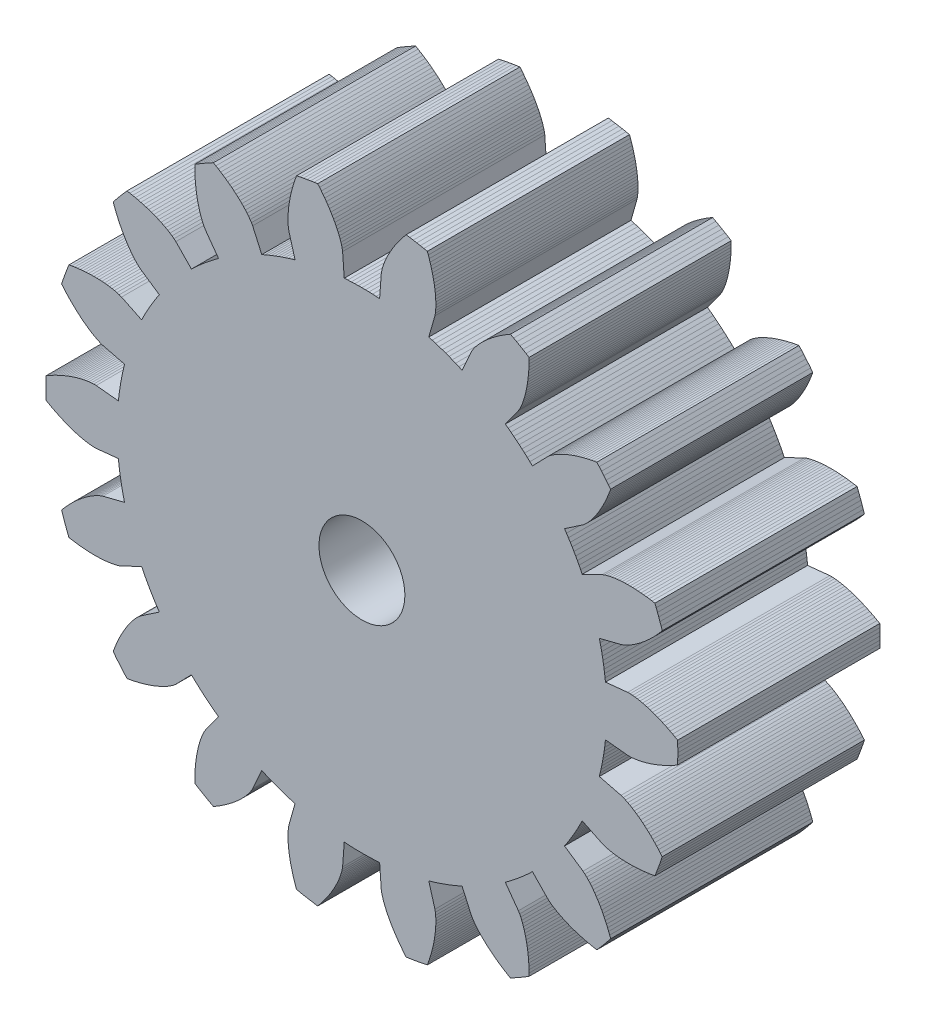
SolidWorks part; units mm, degrees
ref_plane "Front Plane" through (0, 0, 0) normal (0, 0, 1) x (1, 0, 0)
ref_plane "Top Plane" through (0, 0, 0) normal (0, 1, 0) x (1, 0, 0)
ref_plane "Right Plane" through (0, 0, 0) normal (1, 0, 0) x (0, 0, -1)
sketch "Gear Profile m1. 25 z18" plane through (0, 0, 0) normal (0, 0, 1) x (1, 0, 0)
  line L0 (9.637, -0.9881) -> (10.5164, -1.0782)
  line L1 (10.5164, -1.0782) -> (10.6132, -1.0794)
  line L2 (10.6132, -1.0794) -> (10.7108, -1.0732)
  line L3 (10.7108, -1.0732) -> (10.8087, -1.0622)
  line L4 (10.8087, -1.0622) -> (10.9071, -1.0471)
  line L5 (10.9071, -1.0471) -> (11.0057, -1.0284)
  line L6 (11.0057, -1.0284) -> (11.1046, -1.0065)
  line L7 (11.1046, -1.0065) -> (11.2036, -0.9815)
  line L8 (11.2036, -0.9815) -> (11.3028, -0.9536)
  line L9 (11.3028, -0.9536) -> (11.4021, -0.923)
  line L10 (11.4021, -0.923) -> (11.5014, -0.8897)
  line L11 (11.5014, -0.8897) -> (11.6008, -0.8539)
  line L12 (11.6008, -0.8539) -> (11.7002, -0.8156)
  line L13 (11.7002, -0.8156) -> (11.7996, -0.7749)
  line L14 (11.7996, -0.7749) -> (11.899, -0.7318)
  line L15 (11.899, -0.7318) -> (11.9983, -0.6864)
  line L16 (11.9983, -0.6864) -> (12.0975, -0.6387)
  line L17 (12.0975, -0.6387) -> (12.1965, -0.5888)
  line L18 (12.1965, -0.5888) -> (12.2954, -0.5367)
  line L19 (12.2954, -0.5367) -> (12.3942, -0.4824)
  line L20 (12.3942, -0.4824) -> (12.4927, -0.426)
  line L21 (12.4927, -0.426) -> (12.4968, -0.284)
  line L22 (12.4968, -0.284) -> (12.4992, -0.142)
  line L23 (12.4992, -0.142) -> (12.5, 0)
  line L24 (12.5, 0) -> (12.4992, 0.142)
  line L25 (12.4992, 0.142) -> (12.4968, 0.284)
  line L26 (12.4968, 0.284) -> (12.4927, 0.426)
  line L27 (12.4927, 0.426) -> (12.3942, 0.4824)
  line L28 (12.3942, 0.4824) -> (12.2954, 0.5367)
  line L29 (12.2954, 0.5367) -> (12.1965, 0.5888)
  line L30 (12.1965, 0.5888) -> (12.0975, 0.6387)
  line L31 (12.0975, 0.6387) -> (11.9983, 0.6864)
  line L32 (11.9983, 0.6864) -> (11.899, 0.7318)
  line L33 (11.899, 0.7318) -> (11.7996, 0.7749)
  line L34 (11.7996, 0.7749) -> (11.7002, 0.8156)
  line L35 (11.7002, 0.8156) -> (11.6008, 0.8539)
  line L36 (11.6008, 0.8539) -> (11.5014, 0.8897)
  line L37 (11.5014, 0.8897) -> (11.4021, 0.923)
  line L38 (11.4021, 0.923) -> (11.3028, 0.9536)
  line L39 (11.3028, 0.9536) -> (11.2036, 0.9815)
  line L40 (11.2036, 0.9815) -> (11.1046, 1.0065)
  line L41 (11.1046, 1.0065) -> (11.0057, 1.0284)
  line L42 (11.0057, 1.0284) -> (10.9071, 1.0471)
  line L43 (10.9071, 1.0471) -> (10.8087, 1.0622)
  line L44 (10.8087, 1.0622) -> (10.7108, 1.0732)
  line L45 (10.7108, 1.0732) -> (10.6132, 1.0794)
  line L46 (10.6132, 1.0794) -> (10.5164, 1.0782)
  line L47 (10.5164, 1.0782) -> (9.637, 0.9881)
  line L48 (9.637, 0.9881) -> (9.6217, 1.1274)
  line L49 (9.6217, 1.1274) -> (9.6043, 1.2665)
  line L50 (9.6043, 1.2665) -> (9.585, 1.4054)
  line L51 (9.585, 1.4054) -> (9.5637, 1.544)
  line L52 (9.5637, 1.544) -> (9.5403, 1.6822)
  line L53 (9.5403, 1.6822) -> (9.515, 1.8201)
  line L54 (9.515, 1.8201) -> (9.4876, 1.9576)
  line L55 (9.4876, 1.9576) -> (9.4583, 2.0947)
  line L56 (9.4583, 2.0947) -> (9.427, 2.2314)
  line L57 (9.427, 2.2314) -> (9.3937, 2.3676)
  line L58 (9.3937, 2.3676) -> (10.251, 2.5836)
  line L59 (10.251, 2.5836) -> (10.3423, 2.6156)
  line L60 (10.3423, 2.6156) -> (10.4319, 2.6548)
  line L61 (10.4319, 2.6548) -> (10.5202, 2.6987)
  line L62 (10.5202, 2.6987) -> (10.6074, 2.7465)
  line L63 (10.6074, 2.7465) -> (10.6937, 2.7978)
  line L64 (10.6937, 2.7978) -> (10.7791, 2.8522)
  line L65 (10.7791, 2.8522) -> (10.8636, 2.9096)
  line L66 (10.8636, 2.9096) -> (10.9473, 2.9697)
  line L67 (10.9473, 2.9697) -> (11.0301, 3.0324)
  line L68 (11.0301, 3.0324) -> (11.1121, 3.0977)
  line L69 (11.1121, 3.0977) -> (11.1932, 3.1653)
  line L70 (11.1932, 3.1653) -> (11.2736, 3.2353)
  line L71 (11.2736, 3.2353) -> (11.353, 3.3075)
  line L72 (11.353, 3.3075) -> (11.4317, 3.382)
  line L73 (11.4317, 3.382) -> (11.5095, 3.4586)
  line L74 (11.5095, 3.4586) -> (11.5864, 3.5373)
  line L75 (11.5864, 3.5373) -> (11.6624, 3.6181)
  line L76 (11.6624, 3.6181) -> (11.7375, 3.7009)
  line L77 (11.7375, 3.7009) -> (11.8117, 3.7857)
  line L78 (11.8117, 3.7857) -> (11.885, 3.8725)
  line L79 (11.885, 3.8725) -> (11.8403, 4.0073)
  line L80 (11.8403, 4.0073) -> (11.794, 4.1415)
  line L81 (11.794, 4.1415) -> (11.7462, 4.2753)
  line L82 (11.7462, 4.2753) -> (11.6968, 4.4084)
  line L83 (11.6968, 4.4084) -> (11.646, 4.541)
  line L84 (11.646, 4.541) -> (11.5936, 4.673)
  line L85 (11.5936, 4.673) -> (11.4817, 4.6924)
  line L86 (11.4817, 4.6924) -> (11.3704, 4.7096)
  line L87 (11.3704, 4.7096) -> (11.2596, 4.7248)
  line L88 (11.2596, 4.7248) -> (11.1494, 4.7378)
  line L89 (11.1494, 4.7378) -> (11.0399, 4.7487)
  line L90 (11.0399, 4.7487) -> (10.9311, 4.7574)
  line L91 (10.9311, 4.7574) -> (10.823, 4.7639)
  line L92 (10.823, 4.7639) -> (10.7157, 4.7681)
  line L93 (10.7157, 4.7681) -> (10.6091, 4.7701)
  line L94 (10.6091, 4.7701) -> (10.5035, 4.7698)
  line L95 (10.5035, 4.7698) -> (10.3987, 4.767)
  line L96 (10.3987, 4.767) -> (10.295, 4.7619)
  line L97 (10.295, 4.7619) -> (10.1923, 4.7541)
  line L98 (10.1923, 4.7541) -> (10.0906, 4.7437)
  line L99 (10.0906, 4.7437) -> (9.9903, 4.7306)
  line L100 (9.9903, 4.7306) -> (9.8912, 4.7144)
  line L101 (9.8912, 4.7144) -> (9.7936, 4.6949)
  line L102 (9.7936, 4.6949) -> (9.6978, 4.6718)
  line L103 (9.6978, 4.6718) -> (9.604, 4.6442)
  line L104 (9.604, 4.6442) -> (9.5134, 4.61)
  line L105 (9.5134, 4.61) -> (8.7179, 4.2245)
  line L106 (8.7179, 4.2245) -> (8.6558, 4.3502)
  line L107 (8.6558, 4.3502) -> (8.592, 4.475)
  line L108 (8.592, 4.475) -> (8.5263, 4.5989)
  line L109 (8.5263, 4.5989) -> (8.4588, 4.7218)
  line L110 (8.4588, 4.7218) -> (8.3896, 4.8438)
  line L111 (8.3896, 4.8438) -> (8.3186, 4.9647)
  line L112 (8.3186, 4.9647) -> (8.2459, 5.0845)
  line L113 (8.2459, 5.0845) -> (8.1715, 5.2033)
  line L114 (8.1715, 5.2033) -> (8.0953, 5.321)
  line L115 (8.0953, 5.321) -> (8.0175, 5.4376)
  line L116 (8.0175, 5.4376) -> (8.7491, 5.9339)
  line L117 (8.7491, 5.9339) -> (8.824, 5.9952)
  line L118 (8.824, 5.9952) -> (8.8948, 6.0626)
  line L119 (8.8948, 6.0626) -> (8.9627, 6.1341)
  line L120 (8.9627, 6.1341) -> (9.0284, 6.2088)
  line L121 (9.0284, 6.2088) -> (9.0919, 6.2865)
  line L122 (9.0919, 6.2865) -> (9.1535, 6.3669)
  line L123 (9.1535, 6.3669) -> (9.2133, 6.4497)
  line L124 (9.2133, 6.4497) -> (9.2714, 6.5348)
  line L125 (9.2714, 6.5348) -> (9.3278, 6.6221)
  line L126 (9.3278, 6.6221) -> (9.3825, 6.7114)
  line L127 (9.3825, 6.7114) -> (9.4356, 6.8027)
  line L128 (9.4356, 6.8027) -> (9.4872, 6.896)
  line L129 (9.4872, 6.896) -> (9.5371, 6.991)
  line L130 (9.5371, 6.991) -> (9.5856, 7.0879)
  line L131 (9.5856, 7.0879) -> (9.6324, 7.1865)
  line L132 (9.6324, 7.1865) -> (9.6778, 7.2868)
  line L133 (9.6778, 7.2868) -> (9.7216, 7.3887)
  line L134 (9.7216, 7.3887) -> (9.7638, 7.4922)
  line L135 (9.7638, 7.4922) -> (9.8046, 7.5973)
  line L136 (9.8046, 7.5973) -> (9.8438, 7.7039)
  line L137 (9.8438, 7.7039) -> (9.7556, 7.8152)
  line L138 (9.7556, 7.8152) -> (9.6662, 7.9255)
  line L139 (9.6662, 7.9255) -> (9.5756, 8.0348)
  line L140 (9.5756, 8.0348) -> (9.4837, 8.1431)
  line L141 (9.4837, 8.1431) -> (9.3905, 8.2503)
  line L142 (9.3905, 8.2503) -> (9.2962, 8.3565)
  line L143 (9.2962, 8.3565) -> (9.1844, 8.3364)
  line L144 (9.1844, 8.3364) -> (9.0739, 8.3145)
  line L145 (9.0739, 8.3145) -> (8.9646, 8.2908)
  line L146 (8.9646, 8.2908) -> (8.8566, 8.2654)
  line L147 (8.8566, 8.2654) -> (8.75, 8.2382)
  line L148 (8.75, 8.2382) -> (8.6447, 8.2091)
  line L149 (8.6447, 8.2091) -> (8.5409, 8.1783)
  line L150 (8.5409, 8.1783) -> (8.4386, 8.1456)
  line L151 (8.4386, 8.1456) -> (8.3379, 8.111)
  line L152 (8.3379, 8.111) -> (8.2387, 8.0745)
  line L153 (8.2387, 8.0745) -> (8.1412, 8.0361)
  line L154 (8.1412, 8.0361) -> (8.0455, 7.9958)
  line L155 (8.0455, 7.9958) -> (7.9516, 7.9534)
  line L156 (7.9516, 7.9534) -> (7.8597, 7.9089)
  line L157 (7.8597, 7.9089) -> (7.7698, 7.8621)
  line L158 (7.7698, 7.8621) -> (7.6823, 7.813)
  line L159 (7.6823, 7.813) -> (7.5972, 7.7614)
  line L160 (7.5972, 7.7614) -> (7.5151, 7.7069)
  line L161 (7.5151, 7.7069) -> (7.4364, 7.6489)
  line L162 (7.4364, 7.6489) -> (7.363, 7.5858)
  line L163 (7.363, 7.5858) -> (6.7472, 6.9514)
  line L164 (6.7472, 6.9514) -> (6.6459, 7.0483)
  line L165 (6.6459, 7.0483) -> (6.5432, 7.1438)
  line L166 (6.5432, 7.1438) -> (6.4392, 7.2377)
  line L167 (6.4392, 7.2377) -> (6.3337, 7.3302)
  line L168 (6.3337, 7.3302) -> (6.227, 7.4211)
  line L169 (6.227, 7.4211) -> (6.119, 7.5104)
  line L170 (6.119, 7.5104) -> (6.0096, 7.5982)
  line L171 (6.0096, 7.5982) -> (5.899, 7.6843)
  line L172 (5.899, 7.6843) -> (5.7872, 7.7689)
  line L173 (5.7872, 7.7689) -> (5.6742, 7.8518)
  line L174 (5.6742, 7.8518) -> (6.192, 8.5684)
  line L175 (6.192, 8.5684) -> (6.2414, 8.6516)
  line L176 (6.2414, 8.6516) -> (6.2848, 8.7392)
  line L177 (6.2848, 8.7392) -> (6.3242, 8.8296)
  line L178 (6.3242, 8.8296) -> (6.3603, 8.9223)
  line L179 (6.3603, 8.9223) -> (6.3935, 9.017)
  line L180 (6.3935, 9.017) -> (6.4239, 9.1136)
  line L181 (6.4239, 9.1136) -> (6.4518, 9.2119)
  line L182 (6.4518, 9.2119) -> (6.4772, 9.3117)
  line L183 (6.4772, 9.3117) -> (6.5003, 9.413)
  line L184 (6.5003, 9.413) -> (6.5212, 9.5157)
  line L185 (6.5212, 9.5157) -> (6.5399, 9.6196)
  line L186 (6.5399, 9.6196) -> (6.5565, 9.7249)
  line L187 (6.5565, 9.7249) -> (6.5709, 9.8313)
  line L188 (6.5709, 9.8313) -> (6.5833, 9.9389)
  line L189 (6.5833, 9.9389) -> (6.5936, 10.0476)
  line L190 (6.5936, 10.0476) -> (6.6019, 10.1573)
  line L191 (6.6019, 10.1573) -> (6.6082, 10.2681)
  line L192 (6.6082, 10.2681) -> (6.6125, 10.3798)
  line L193 (6.6125, 10.3798) -> (6.6149, 10.4925)
  line L194 (6.6149, 10.4925) -> (6.6153, 10.6061)
  line L195 (6.6153, 10.6061) -> (6.4943, 10.6805)
  line L196 (6.4943, 10.6805) -> (6.3726, 10.7536)
  line L197 (6.3726, 10.7536) -> (6.25, 10.8253)
  line L198 (6.25, 10.8253) -> (6.1266, 10.8956)
  line L199 (6.1266, 10.8956) -> (6.0024, 10.9645)
  line L200 (6.0024, 10.9645) -> (5.8775, 11.032)
  line L201 (5.8775, 11.032) -> (5.7793, 10.9749)
  line L202 (5.7793, 10.9749) -> (5.6829, 10.9165)
  line L203 (5.6829, 10.9165) -> (5.5883, 10.8569)
  line L204 (5.5883, 10.8569) -> (5.4956, 10.7961)
  line L205 (5.4956, 10.7961) -> (5.4047, 10.734)
  line L206 (5.4047, 10.734) -> (5.3157, 10.6707)
  line L207 (5.3157, 10.6707) -> (5.2287, 10.6062)
  line L208 (5.2287, 10.6062) -> (5.1438, 10.5405)
  line L209 (5.1438, 10.5405) -> (5.0609, 10.4735)
  line L210 (5.0609, 10.4735) -> (4.9802, 10.4054)
  line L211 (4.9802, 10.4054) -> (4.9017, 10.336)
  line L212 (4.9017, 10.336) -> (4.8255, 10.2653)
  line L213 (4.8255, 10.2653) -> (4.7518, 10.1933)
  line L214 (4.7518, 10.1933) -> (4.6807, 10.1201)
  line L215 (4.6807, 10.1201) -> (4.6122, 10.0454)
  line L216 (4.6122, 10.0454) -> (4.5468, 9.9694)
  line L217 (4.5468, 9.9694) -> (4.4845, 9.8917)
  line L218 (4.4845, 9.8917) -> (4.4259, 9.8124)
  line L219 (4.4259, 9.8124) -> (4.3718, 9.731)
  line L220 (4.3718, 9.731) -> (4.3244, 9.6466)
  line L221 (4.3244, 9.6466) -> (3.9628, 8.8399)
  line L222 (3.9628, 8.8399) -> (3.8345, 8.8963)
  line L223 (3.8345, 8.8963) -> (3.7053, 8.9509)
  line L224 (3.7053, 8.9509) -> (3.5754, 9.0036)
  line L225 (3.5754, 9.0036) -> (3.4447, 9.0544)
  line L226 (3.4447, 9.0544) -> (3.3133, 9.1033)
  line L227 (3.3133, 9.1033) -> (3.1812, 9.1503)
  line L228 (3.1812, 9.1503) -> (3.0485, 9.1953)
  line L229 (3.0485, 9.1953) -> (2.9151, 9.2385)
  line L230 (2.9151, 9.2385) -> (2.7811, 9.2797)
  line L231 (2.7811, 9.2797) -> (2.6465, 9.319)
  line L232 (2.6465, 9.319) -> (2.888, 10.1694)
  line L233 (2.888, 10.1694) -> (2.9059, 10.2645)
  line L234 (2.9059, 10.2645) -> (2.9168, 10.3617)
  line L235 (2.9168, 10.3617) -> (2.923, 10.4601)
  line L236 (2.923, 10.4601) -> (2.9252, 10.5596)
  line L237 (2.9252, 10.5596) -> (2.9239, 10.6599)
  line L238 (2.9239, 10.6599) -> (2.9195, 10.7611)
  line L239 (2.9195, 10.7611) -> (2.912, 10.863)
  line L240 (2.912, 10.863) -> (2.9018, 10.9655)
  line L241 (2.9018, 10.9655) -> (2.8889, 11.0686)
  line L242 (2.8889, 11.0686) -> (2.8734, 11.1722)
  line L243 (2.8734, 11.1722) -> (2.8554, 11.2763)
  line L244 (2.8554, 11.2763) -> (2.8349, 11.3808)
  line L245 (2.8349, 11.3808) -> (2.8121, 11.4858)
  line L246 (2.8121, 11.4858) -> (2.7869, 11.5911)
  line L247 (2.7869, 11.5911) -> (2.7595, 11.6968)
  line L248 (2.7595, 11.6968) -> (2.7297, 11.8028)
  line L249 (2.7297, 11.8028) -> (2.6978, 11.909)
  line L250 (2.6978, 11.909) -> (2.6636, 12.0155)
  line L251 (2.6636, 12.0155) -> (2.6273, 12.1221)
  line L252 (2.6273, 12.1221) -> (2.5888, 12.229)
  line L253 (2.5888, 12.229) -> (2.4497, 12.2576)
  line L254 (2.4497, 12.2576) -> (2.3103, 12.2846)
  line L255 (2.3103, 12.2846) -> (2.1706, 12.3101)
  line L256 (2.1706, 12.3101) -> (2.0306, 12.334)
  line L257 (2.0306, 12.334) -> (1.8904, 12.3562)
  line L258 (1.8904, 12.3562) -> (1.7499, 12.3769)
  line L259 (1.7499, 12.3769) -> (1.6771, 12.2897)
  line L260 (1.6771, 12.2897) -> (1.6065, 12.2018)
  line L261 (1.6065, 12.2018) -> (1.538, 12.1135)
  line L262 (1.538, 12.1135) -> (1.4717, 12.0246)
  line L263 (1.4717, 12.0246) -> (1.4075, 11.9352)
  line L264 (1.4075, 11.9352) -> (1.3455, 11.8453)
  line L265 (1.3455, 11.8453) -> (1.2859, 11.7549)
  line L266 (1.2859, 11.7549) -> (1.2285, 11.6641)
  line L267 (1.2285, 11.6641) -> (1.1735, 11.5728)
  line L268 (1.1735, 11.5728) -> (1.121, 11.4812)
  line L269 (1.121, 11.4812) -> (1.071, 11.3891)
  line L270 (1.071, 11.3891) -> (1.0236, 11.2966)
  line L271 (1.0236, 11.2966) -> (0.9789, 11.2038)
  line L272 (0.9789, 11.2038) -> (0.9371, 11.1106)
  line L273 (0.9371, 11.1106) -> (0.8983, 11.0171)
  line L274 (0.8983, 11.0171) -> (0.8628, 10.9232)
  line L275 (0.8628, 10.9232) -> (0.8309, 10.829)
  line L276 (0.8309, 10.829) -> (0.803, 10.7344)
  line L277 (0.803, 10.7344) -> (0.78, 10.6394)
  line L278 (0.78, 10.6394) -> (0.7643, 10.5439)
  line L279 (0.7643, 10.5439) -> (0.7004, 9.6621)
  line L280 (0.7004, 9.6621) -> (0.5605, 9.6713)
  line L281 (0.5605, 9.6713) -> (0.4205, 9.6784)
  line L282 (0.4205, 9.6784) -> (0.2804, 9.6834)
  line L283 (0.2804, 9.6834) -> (0.1402, 9.6865)
  line L284 (0.1402, 9.6865) -> (0, 9.6875)
  line L285 (0, 9.6875) -> (-0.1402, 9.6865)
  line L286 (-0.1402, 9.6865) -> (-0.2804, 9.6834)
  line L287 (-0.2804, 9.6834) -> (-0.4205, 9.6784)
  line L288 (-0.4205, 9.6784) -> (-0.5605, 9.6713)
  line L289 (-0.5605, 9.6713) -> (-0.7004, 9.6621)
  line L290 (-0.7004, 9.6621) -> (-0.7643, 10.5439)
  line L291 (-0.7643, 10.5439) -> (-0.78, 10.6394)
  line L292 (-0.78, 10.6394) -> (-0.803, 10.7344)
  line L293 (-0.803, 10.7344) -> (-0.8309, 10.829)
  line L294 (-0.8309, 10.829) -> (-0.8628, 10.9232)
  line L295 (-0.8628, 10.9232) -> (-0.8983, 11.0171)
  line L296 (-0.8983, 11.0171) -> (-0.9371, 11.1106)
  line L297 (-0.9371, 11.1106) -> (-0.9789, 11.2038)
  line L298 (-0.9789, 11.2038) -> (-1.0236, 11.2966)
  line L299 (-1.0236, 11.2966) -> (-1.071, 11.3891)
  line L300 (-1.071, 11.3891) -> (-1.121, 11.4812)
  line L301 (-1.121, 11.4812) -> (-1.1735, 11.5728)
  line L302 (-1.1735, 11.5728) -> (-1.2285, 11.6641)
  line L303 (-1.2285, 11.6641) -> (-1.2859, 11.7549)
  line L304 (-1.2859, 11.7549) -> (-1.3455, 11.8453)
  line L305 (-1.3455, 11.8453) -> (-1.4075, 11.9352)
  line L306 (-1.4075, 11.9352) -> (-1.4717, 12.0246)
  line L307 (-1.4717, 12.0246) -> (-1.538, 12.1135)
  line L308 (-1.538, 12.1135) -> (-1.6065, 12.2018)
  line L309 (-1.6065, 12.2018) -> (-1.6771, 12.2897)
  line L310 (-1.6771, 12.2897) -> (-1.7499, 12.3769)
  line L311 (-1.7499, 12.3769) -> (-1.8904, 12.3562)
  line L312 (-1.8904, 12.3562) -> (-2.0306, 12.334)
  line L313 (-2.0306, 12.334) -> (-2.1706, 12.3101)
  line L314 (-2.1706, 12.3101) -> (-2.3103, 12.2846)
  line L315 (-2.3103, 12.2846) -> (-2.4497, 12.2576)
  line L316 (-2.4497, 12.2576) -> (-2.5888, 12.229)
  line L317 (-2.5888, 12.229) -> (-2.6273, 12.1221)
  line L318 (-2.6273, 12.1221) -> (-2.6636, 12.0155)
  line L319 (-2.6636, 12.0155) -> (-2.6978, 11.909)
  line L320 (-2.6978, 11.909) -> (-2.7297, 11.8028)
  line L321 (-2.7297, 11.8028) -> (-2.7595, 11.6968)
  line L322 (-2.7595, 11.6968) -> (-2.7869, 11.5911)
  line L323 (-2.7869, 11.5911) -> (-2.8121, 11.4858)
  line L324 (-2.8121, 11.4858) -> (-2.8349, 11.3808)
  line L325 (-2.8349, 11.3808) -> (-2.8554, 11.2763)
  line L326 (-2.8554, 11.2763) -> (-2.8734, 11.1722)
  line L327 (-2.8734, 11.1722) -> (-2.8889, 11.0686)
  line L328 (-2.8889, 11.0686) -> (-2.9018, 10.9655)
  line L329 (-2.9018, 10.9655) -> (-2.912, 10.863)
  line L330 (-2.912, 10.863) -> (-2.9195, 10.7611)
  line L331 (-2.9195, 10.7611) -> (-2.9239, 10.6599)
  line L332 (-2.9239, 10.6599) -> (-2.9252, 10.5596)
  line L333 (-2.9252, 10.5596) -> (-2.923, 10.4601)
  line L334 (-2.923, 10.4601) -> (-2.9168, 10.3617)
  line L335 (-2.9168, 10.3617) -> (-2.9059, 10.2645)
  line L336 (-2.9059, 10.2645) -> (-2.888, 10.1694)
  line L337 (-2.888, 10.1694) -> (-2.6465, 9.319)
  line L338 (-2.6465, 9.319) -> (-2.7811, 9.2797)
  line L339 (-2.7811, 9.2797) -> (-2.9151, 9.2385)
  line L340 (-2.9151, 9.2385) -> (-3.0485, 9.1953)
  line L341 (-3.0485, 9.1953) -> (-3.1812, 9.1503)
  line L342 (-3.1812, 9.1503) -> (-3.3133, 9.1033)
  line L343 (-3.3133, 9.1033) -> (-3.4447, 9.0544)
  line L344 (-3.4447, 9.0544) -> (-3.5754, 9.0036)
  line L345 (-3.5754, 9.0036) -> (-3.7053, 8.9509)
  line L346 (-3.7053, 8.9509) -> (-3.8345, 8.8963)
  line L347 (-3.8345, 8.8963) -> (-3.9628, 8.8399)
  line L348 (-3.9628, 8.8399) -> (-4.3244, 9.6466)
  line L349 (-4.3244, 9.6466) -> (-4.3718, 9.731)
  line L350 (-4.3718, 9.731) -> (-4.4259, 9.8124)
  line L351 (-4.4259, 9.8124) -> (-4.4845, 9.8917)
  line L352 (-4.4845, 9.8917) -> (-4.5468, 9.9694)
  line L353 (-4.5468, 9.9694) -> (-4.6122, 10.0454)
  line L354 (-4.6122, 10.0454) -> (-4.6807, 10.1201)
  line L355 (-4.6807, 10.1201) -> (-4.7518, 10.1933)
  line L356 (-4.7518, 10.1933) -> (-4.8255, 10.2653)
  line L357 (-4.8255, 10.2653) -> (-4.9017, 10.336)
  line L358 (-4.9017, 10.336) -> (-4.9802, 10.4054)
  line L359 (-4.9802, 10.4054) -> (-5.0609, 10.4735)
  line L360 (-5.0609, 10.4735) -> (-5.1438, 10.5405)
  line L361 (-5.1438, 10.5405) -> (-5.2287, 10.6062)
  line L362 (-5.2287, 10.6062) -> (-5.3157, 10.6707)
  line L363 (-5.3157, 10.6707) -> (-5.4047, 10.734)
  line L364 (-5.4047, 10.734) -> (-5.4956, 10.7961)
  line L365 (-5.4956, 10.7961) -> (-5.5883, 10.8569)
  line L366 (-5.5883, 10.8569) -> (-5.6829, 10.9165)
  line L367 (-5.6829, 10.9165) -> (-5.7793, 10.9749)
  line L368 (-5.7793, 10.9749) -> (-5.8775, 11.032)
  line L369 (-5.8775, 11.032) -> (-6.0024, 10.9645)
  line L370 (-6.0024, 10.9645) -> (-6.1266, 10.8956)
  line L371 (-6.1266, 10.8956) -> (-6.25, 10.8253)
  line L372 (-6.25, 10.8253) -> (-6.3726, 10.7536)
  line L373 (-6.3726, 10.7536) -> (-6.4943, 10.6805)
  line L374 (-6.4943, 10.6805) -> (-6.6153, 10.6061)
  line L375 (-6.6153, 10.6061) -> (-6.6149, 10.4925)
  line L376 (-6.6149, 10.4925) -> (-6.6125, 10.3798)
  line L377 (-6.6125, 10.3798) -> (-6.6082, 10.2681)
  line L378 (-6.6082, 10.2681) -> (-6.6019, 10.1573)
  line L379 (-6.6019, 10.1573) -> (-6.5936, 10.0476)
  line L380 (-6.5936, 10.0476) -> (-6.5833, 9.9389)
  line L381 (-6.5833, 9.9389) -> (-6.5709, 9.8313)
  line L382 (-6.5709, 9.8313) -> (-6.5565, 9.7249)
  line L383 (-6.5565, 9.7249) -> (-6.5399, 9.6196)
  line L384 (-6.5399, 9.6196) -> (-6.5212, 9.5157)
  line L385 (-6.5212, 9.5157) -> (-6.5003, 9.413)
  line L386 (-6.5003, 9.413) -> (-6.4772, 9.3117)
  line L387 (-6.4772, 9.3117) -> (-6.4518, 9.2119)
  line L388 (-6.4518, 9.2119) -> (-6.4239, 9.1136)
  line L389 (-6.4239, 9.1136) -> (-6.3935, 9.017)
  line L390 (-6.3935, 9.017) -> (-6.3603, 8.9223)
  line L391 (-6.3603, 8.9223) -> (-6.3242, 8.8296)
  line L392 (-6.3242, 8.8296) -> (-6.2848, 8.7392)
  line L393 (-6.2848, 8.7392) -> (-6.2414, 8.6516)
  line L394 (-6.2414, 8.6516) -> (-6.192, 8.5684)
  line L395 (-6.192, 8.5684) -> (-5.6742, 7.8518)
  line L396 (-5.6742, 7.8518) -> (-5.7872, 7.7689)
  line L397 (-5.7872, 7.7689) -> (-5.899, 7.6843)
  line L398 (-5.899, 7.6843) -> (-6.0096, 7.5982)
  line L399 (-6.0096, 7.5982) -> (-6.119, 7.5104)
  line L400 (-6.119, 7.5104) -> (-6.227, 7.4211)
  line L401 (-6.227, 7.4211) -> (-6.3337, 7.3302)
  line L402 (-6.3337, 7.3302) -> (-6.4392, 7.2377)
  line L403 (-6.4392, 7.2377) -> (-6.5432, 7.1438)
  line L404 (-6.5432, 7.1438) -> (-6.6459, 7.0483)
  line L405 (-6.6459, 7.0483) -> (-6.7472, 6.9514)
  line L406 (-6.7472, 6.9514) -> (-7.363, 7.5858)
  line L407 (-7.363, 7.5858) -> (-7.4364, 7.6489)
  line L408 (-7.4364, 7.6489) -> (-7.5151, 7.7069)
  line L409 (-7.5151, 7.7069) -> (-7.5972, 7.7614)
  line L410 (-7.5972, 7.7614) -> (-7.6823, 7.813)
  line L411 (-7.6823, 7.813) -> (-7.7698, 7.8621)
  line L412 (-7.7698, 7.8621) -> (-7.8597, 7.9089)
  line L413 (-7.8597, 7.9089) -> (-7.9516, 7.9534)
  line L414 (-7.9516, 7.9534) -> (-8.0455, 7.9958)
  line L415 (-8.0455, 7.9958) -> (-8.1412, 8.0361)
  line L416 (-8.1412, 8.0361) -> (-8.2387, 8.0745)
  line L417 (-8.2387, 8.0745) -> (-8.3379, 8.111)
  line L418 (-8.3379, 8.111) -> (-8.4386, 8.1456)
  line L419 (-8.4386, 8.1456) -> (-8.5409, 8.1783)
  line L420 (-8.5409, 8.1783) -> (-8.6447, 8.2091)
  line L421 (-8.6447, 8.2091) -> (-8.75, 8.2382)
  line L422 (-8.75, 8.2382) -> (-8.8566, 8.2654)
  line L423 (-8.8566, 8.2654) -> (-8.9646, 8.2908)
  line L424 (-8.9646, 8.2908) -> (-9.0739, 8.3145)
  line L425 (-9.0739, 8.3145) -> (-9.1844, 8.3364)
  line L426 (-9.1844, 8.3364) -> (-9.2962, 8.3565)
  line L427 (-9.2962, 8.3565) -> (-9.3905, 8.2503)
  line L428 (-9.3905, 8.2503) -> (-9.4837, 8.1431)
  line L429 (-9.4837, 8.1431) -> (-9.5756, 8.0348)
  line L430 (-9.5756, 8.0348) -> (-9.6662, 7.9255)
  line L431 (-9.6662, 7.9255) -> (-9.7556, 7.8152)
  line L432 (-9.7556, 7.8152) -> (-9.8438, 7.7039)
  line L433 (-9.8438, 7.7039) -> (-9.8046, 7.5973)
  line L434 (-9.8046, 7.5973) -> (-9.7638, 7.4922)
  line L435 (-9.7638, 7.4922) -> (-9.7216, 7.3887)
  line L436 (-9.7216, 7.3887) -> (-9.6778, 7.2868)
  line L437 (-9.6778, 7.2868) -> (-9.6324, 7.1865)
  line L438 (-9.6324, 7.1865) -> (-9.5856, 7.0879)
  line L439 (-9.5856, 7.0879) -> (-9.5371, 6.991)
  line L440 (-9.5371, 6.991) -> (-9.4872, 6.896)
  line L441 (-9.4872, 6.896) -> (-9.4356, 6.8027)
  line L442 (-9.4356, 6.8027) -> (-9.3825, 6.7114)
  line L443 (-9.3825, 6.7114) -> (-9.3278, 6.6221)
  line L444 (-9.3278, 6.6221) -> (-9.2714, 6.5348)
  line L445 (-9.2714, 6.5348) -> (-9.2133, 6.4497)
  line L446 (-9.2133, 6.4497) -> (-9.1535, 6.3669)
  line L447 (-9.1535, 6.3669) -> (-9.0919, 6.2865)
  line L448 (-9.0919, 6.2865) -> (-9.0284, 6.2088)
  line L449 (-9.0284, 6.2088) -> (-8.9627, 6.1341)
  line L450 (-8.9627, 6.1341) -> (-8.8948, 6.0626)
  line L451 (-8.8948, 6.0626) -> (-8.824, 5.9952)
  line L452 (-8.824, 5.9952) -> (-8.7491, 5.9339)
  line L453 (-8.7491, 5.9339) -> (-8.0175, 5.4376)
  line L454 (-8.0175, 5.4376) -> (-8.0953, 5.321)
  line L455 (-8.0953, 5.321) -> (-8.1715, 5.2033)
  line L456 (-8.1715, 5.2033) -> (-8.2459, 5.0845)
  line L457 (-8.2459, 5.0845) -> (-8.3186, 4.9647)
  line L458 (-8.3186, 4.9647) -> (-8.3896, 4.8438)
  line L459 (-8.3896, 4.8438) -> (-8.4588, 4.7218)
  line L460 (-8.4588, 4.7218) -> (-8.5263, 4.5989)
  line L461 (-8.5263, 4.5989) -> (-8.592, 4.475)
  line L462 (-8.592, 4.475) -> (-8.6558, 4.3502)
  line L463 (-8.6558, 4.3502) -> (-8.7179, 4.2245)
  line L464 (-8.7179, 4.2245) -> (-9.5134, 4.61)
  line L465 (-9.5134, 4.61) -> (-9.604, 4.6442)
  line L466 (-9.604, 4.6442) -> (-9.6978, 4.6718)
  line L467 (-9.6978, 4.6718) -> (-9.7936, 4.6949)
  line L468 (-9.7936, 4.6949) -> (-9.8912, 4.7144)
  line L469 (-9.8912, 4.7144) -> (-9.9903, 4.7306)
  line L470 (-9.9903, 4.7306) -> (-10.0906, 4.7437)
  line L471 (-10.0906, 4.7437) -> (-10.1923, 4.7541)
  line L472 (-10.1923, 4.7541) -> (-10.295, 4.7619)
  line L473 (-10.295, 4.7619) -> (-10.3987, 4.767)
  line L474 (-10.3987, 4.767) -> (-10.5035, 4.7698)
  line L475 (-10.5035, 4.7698) -> (-10.6091, 4.7701)
  line L476 (-10.6091, 4.7701) -> (-10.7157, 4.7681)
  line L477 (-10.7157, 4.7681) -> (-10.823, 4.7639)
  line L478 (-10.823, 4.7639) -> (-10.9311, 4.7574)
  line L479 (-10.9311, 4.7574) -> (-11.0399, 4.7487)
  line L480 (-11.0399, 4.7487) -> (-11.1494, 4.7378)
  line L481 (-11.1494, 4.7378) -> (-11.2596, 4.7248)
  line L482 (-11.2596, 4.7248) -> (-11.3704, 4.7096)
  line L483 (-11.3704, 4.7096) -> (-11.4817, 4.6924)
  line L484 (-11.4817, 4.6924) -> (-11.5936, 4.673)
  line L485 (-11.5936, 4.673) -> (-11.646, 4.541)
  line L486 (-11.646, 4.541) -> (-11.6968, 4.4084)
  line L487 (-11.6968, 4.4084) -> (-11.7462, 4.2753)
  line L488 (-11.7462, 4.2753) -> (-11.794, 4.1415)
  line L489 (-11.794, 4.1415) -> (-11.8403, 4.0073)
  line L490 (-11.8403, 4.0073) -> (-11.885, 3.8725)
  line L491 (-11.885, 3.8725) -> (-11.8117, 3.7857)
  line L492 (-11.8117, 3.7857) -> (-11.7375, 3.7009)
  line L493 (-11.7375, 3.7009) -> (-11.6624, 3.6181)
  line L494 (-11.6624, 3.6181) -> (-11.5864, 3.5373)
  line L495 (-11.5864, 3.5373) -> (-11.5095, 3.4586)
  line L496 (-11.5095, 3.4586) -> (-11.4317, 3.382)
  line L497 (-11.4317, 3.382) -> (-11.353, 3.3075)
  line L498 (-11.353, 3.3075) -> (-11.2736, 3.2353)
  line L499 (-11.2736, 3.2353) -> (-11.1932, 3.1653)
  line L500 (-11.1932, 3.1653) -> (-11.1121, 3.0977)
  line L501 (-11.1121, 3.0977) -> (-11.0301, 3.0324)
  line L502 (-11.0301, 3.0324) -> (-10.9473, 2.9697)
  line L503 (-10.9473, 2.9697) -> (-10.8636, 2.9096)
  line L504 (-10.8636, 2.9096) -> (-10.7791, 2.8522)
  line L505 (-10.7791, 2.8522) -> (-10.6937, 2.7978)
  line L506 (-10.6937, 2.7978) -> (-10.6074, 2.7465)
  line L507 (-10.6074, 2.7465) -> (-10.5202, 2.6987)
  line L508 (-10.5202, 2.6987) -> (-10.4319, 2.6548)
  line L509 (-10.4319, 2.6548) -> (-10.3423, 2.6156)
  line L510 (-10.3423, 2.6156) -> (-10.251, 2.5836)
  line L511 (-10.251, 2.5836) -> (-9.3937, 2.3676)
  line L512 (-9.3937, 2.3676) -> (-9.427, 2.2314)
  line L513 (-9.427, 2.2314) -> (-9.4583, 2.0947)
  line L514 (-9.4583, 2.0947) -> (-9.4876, 1.9576)
  line L515 (-9.4876, 1.9576) -> (-9.515, 1.8201)
  line L516 (-9.515, 1.8201) -> (-9.5403, 1.6822)
  line L517 (-9.5403, 1.6822) -> (-9.5637, 1.544)
  line L518 (-9.5637, 1.544) -> (-9.585, 1.4054)
  line L519 (-9.585, 1.4054) -> (-9.6043, 1.2665)
  line L520 (-9.6043, 1.2665) -> (-9.6217, 1.1274)
  line L521 (-9.6217, 1.1274) -> (-9.637, 0.9881)
  line L522 (-9.637, 0.9881) -> (-10.5164, 1.0782)
  line L523 (-10.5164, 1.0782) -> (-10.6132, 1.0794)
  line L524 (-10.6132, 1.0794) -> (-10.7108, 1.0732)
  line L525 (-10.7108, 1.0732) -> (-10.8087, 1.0622)
  line L526 (-10.8087, 1.0622) -> (-10.9071, 1.0471)
  line L527 (-10.9071, 1.0471) -> (-11.0057, 1.0284)
  line L528 (-11.0057, 1.0284) -> (-11.1046, 1.0065)
  line L529 (-11.1046, 1.0065) -> (-11.2036, 0.9815)
  line L530 (-11.2036, 0.9815) -> (-11.3028, 0.9536)
  line L531 (-11.3028, 0.9536) -> (-11.4021, 0.923)
  line L532 (-11.4021, 0.923) -> (-11.5014, 0.8897)
  line L533 (-11.5014, 0.8897) -> (-11.6008, 0.8539)
  line L534 (-11.6008, 0.8539) -> (-11.7002, 0.8156)
  line L535 (-11.7002, 0.8156) -> (-11.7996, 0.7749)
  line L536 (-11.7996, 0.7749) -> (-11.899, 0.7318)
  line L537 (-11.899, 0.7318) -> (-11.9983, 0.6864)
  line L538 (-11.9983, 0.6864) -> (-12.0975, 0.6387)
  line L539 (-12.0975, 0.6387) -> (-12.1965, 0.5888)
  line L540 (-12.1965, 0.5888) -> (-12.2954, 0.5367)
  line L541 (-12.2954, 0.5367) -> (-12.3942, 0.4824)
  line L542 (-12.3942, 0.4824) -> (-12.4927, 0.426)
  line L543 (-12.4927, 0.426) -> (-12.4968, 0.284)
  line L544 (-12.4968, 0.284) -> (-12.4992, 0.142)
  line L545 (-12.4992, 0.142) -> (-12.5, 0)
  line L546 (-12.5, 0) -> (-12.4992, -0.142)
  line L547 (-12.4992, -0.142) -> (-12.4968, -0.284)
  line L548 (-12.4968, -0.284) -> (-12.4927, -0.426)
  line L549 (-12.4927, -0.426) -> (-12.3942, -0.4824)
  line L550 (-12.3942, -0.4824) -> (-12.2954, -0.5367)
  line L551 (-12.2954, -0.5367) -> (-12.1965, -0.5888)
  line L552 (-12.1965, -0.5888) -> (-12.0975, -0.6387)
  line L553 (-12.0975, -0.6387) -> (-11.9983, -0.6864)
  line L554 (-11.9983, -0.6864) -> (-11.899, -0.7318)
  line L555 (-11.899, -0.7318) -> (-11.7996, -0.7749)
  line L556 (-11.7996, -0.7749) -> (-11.7002, -0.8156)
  line L557 (-11.7002, -0.8156) -> (-11.6008, -0.8539)
  line L558 (-11.6008, -0.8539) -> (-11.5014, -0.8897)
  line L559 (-11.5014, -0.8897) -> (-11.4021, -0.923)
  line L560 (-11.4021, -0.923) -> (-11.3028, -0.9536)
  line L561 (-11.3028, -0.9536) -> (-11.2036, -0.9815)
  line L562 (-11.2036, -0.9815) -> (-11.1046, -1.0065)
  line L563 (-11.1046, -1.0065) -> (-11.0057, -1.0284)
  line L564 (-11.0057, -1.0284) -> (-10.9071, -1.0471)
  line L565 (-10.9071, -1.0471) -> (-10.8087, -1.0622)
  line L566 (-10.8087, -1.0622) -> (-10.7108, -1.0732)
  line L567 (-10.7108, -1.0732) -> (-10.6132, -1.0794)
  line L568 (-10.6132, -1.0794) -> (-10.5164, -1.0782)
  line L569 (-10.5164, -1.0782) -> (-9.637, -0.9881)
  line L570 (-9.637, -0.9881) -> (-9.6217, -1.1274)
  line L571 (-9.6217, -1.1274) -> (-9.6043, -1.2665)
  line L572 (-9.6043, -1.2665) -> (-9.585, -1.4054)
  line L573 (-9.585, -1.4054) -> (-9.5637, -1.544)
  line L574 (-9.5637, -1.544) -> (-9.5403, -1.6822)
  line L575 (-9.5403, -1.6822) -> (-9.515, -1.8201)
  line L576 (-9.515, -1.8201) -> (-9.4876, -1.9576)
  line L577 (-9.4876, -1.9576) -> (-9.4583, -2.0947)
  line L578 (-9.4583, -2.0947) -> (-9.427, -2.2314)
  line L579 (-9.427, -2.2314) -> (-9.3937, -2.3676)
  line L580 (-9.3937, -2.3676) -> (-10.251, -2.5836)
  line L581 (-10.251, -2.5836) -> (-10.3423, -2.6156)
  line L582 (-10.3423, -2.6156) -> (-10.4319, -2.6548)
  line L583 (-10.4319, -2.6548) -> (-10.5202, -2.6987)
  line L584 (-10.5202, -2.6987) -> (-10.6074, -2.7465)
  line L585 (-10.6074, -2.7465) -> (-10.6937, -2.7978)
  line L586 (-10.6937, -2.7978) -> (-10.7791, -2.8522)
  line L587 (-10.7791, -2.8522) -> (-10.8636, -2.9096)
  line L588 (-10.8636, -2.9096) -> (-10.9473, -2.9697)
  line L589 (-10.9473, -2.9697) -> (-11.0301, -3.0324)
  line L590 (-11.0301, -3.0324) -> (-11.1121, -3.0977)
  line L591 (-11.1121, -3.0977) -> (-11.1932, -3.1653)
  line L592 (-11.1932, -3.1653) -> (-11.2736, -3.2353)
  line L593 (-11.2736, -3.2353) -> (-11.353, -3.3075)
  line L594 (-11.353, -3.3075) -> (-11.4317, -3.382)
  line L595 (-11.4317, -3.382) -> (-11.5095, -3.4586)
  line L596 (-11.5095, -3.4586) -> (-11.5864, -3.5373)
  line L597 (-11.5864, -3.5373) -> (-11.6624, -3.6181)
  line L598 (-11.6624, -3.6181) -> (-11.7375, -3.7009)
  line L599 (-11.7375, -3.7009) -> (-11.8117, -3.7857)
  line L600 (-11.8117, -3.7857) -> (-11.885, -3.8725)
  line L601 (-11.885, -3.8725) -> (-11.8403, -4.0073)
  line L602 (-11.8403, -4.0073) -> (-11.794, -4.1415)
  line L603 (-11.794, -4.1415) -> (-11.7462, -4.2753)
  line L604 (-11.7462, -4.2753) -> (-11.6968, -4.4084)
  line L605 (-11.6968, -4.4084) -> (-11.646, -4.541)
  line L606 (-11.646, -4.541) -> (-11.5936, -4.673)
  line L607 (-11.5936, -4.673) -> (-11.4817, -4.6924)
  line L608 (-11.4817, -4.6924) -> (-11.3704, -4.7096)
  line L609 (-11.3704, -4.7096) -> (-11.2596, -4.7248)
  line L610 (-11.2596, -4.7248) -> (-11.1494, -4.7378)
  line L611 (-11.1494, -4.7378) -> (-11.0399, -4.7487)
  line L612 (-11.0399, -4.7487) -> (-10.9311, -4.7574)
  line L613 (-10.9311, -4.7574) -> (-10.823, -4.7639)
  line L614 (-10.823, -4.7639) -> (-10.7157, -4.7681)
  line L615 (-10.7157, -4.7681) -> (-10.6091, -4.7701)
  line L616 (-10.6091, -4.7701) -> (-10.5035, -4.7698)
  line L617 (-10.5035, -4.7698) -> (-10.3987, -4.767)
  line L618 (-10.3987, -4.767) -> (-10.295, -4.7619)
  line L619 (-10.295, -4.7619) -> (-10.1923, -4.7541)
  line L620 (-10.1923, -4.7541) -> (-10.0906, -4.7437)
  line L621 (-10.0906, -4.7437) -> (-9.9903, -4.7306)
  line L622 (-9.9903, -4.7306) -> (-9.8912, -4.7144)
  line L623 (-9.8912, -4.7144) -> (-9.7936, -4.6949)
  line L624 (-9.7936, -4.6949) -> (-9.6978, -4.6718)
  line L625 (-9.6978, -4.6718) -> (-9.604, -4.6442)
  line L626 (-9.604, -4.6442) -> (-9.5134, -4.61)
  line L627 (-9.5134, -4.61) -> (-8.7179, -4.2245)
  line L628 (-8.7179, -4.2245) -> (-8.6558, -4.3502)
  line L629 (-8.6558, -4.3502) -> (-8.592, -4.475)
  line L630 (-8.592, -4.475) -> (-8.5263, -4.5989)
  line L631 (-8.5263, -4.5989) -> (-8.4588, -4.7218)
  line L632 (-8.4588, -4.7218) -> (-8.3896, -4.8438)
  line L633 (-8.3896, -4.8438) -> (-8.3186, -4.9647)
  line L634 (-8.3186, -4.9647) -> (-8.2459, -5.0845)
  line L635 (-8.2459, -5.0845) -> (-8.1715, -5.2033)
  line L636 (-8.1715, -5.2033) -> (-8.0953, -5.321)
  line L637 (-8.0953, -5.321) -> (-8.0175, -5.4376)
  line L638 (-8.0175, -5.4376) -> (-8.7491, -5.9339)
  line L639 (-8.7491, -5.9339) -> (-8.824, -5.9952)
  line L640 (-8.824, -5.9952) -> (-8.8948, -6.0626)
  line L641 (-8.8948, -6.0626) -> (-8.9627, -6.1341)
  line L642 (-8.9627, -6.1341) -> (-9.0284, -6.2088)
  line L643 (-9.0284, -6.2088) -> (-9.0919, -6.2865)
  line L644 (-9.0919, -6.2865) -> (-9.1535, -6.3669)
  line L645 (-9.1535, -6.3669) -> (-9.2133, -6.4497)
  line L646 (-9.2133, -6.4497) -> (-9.2714, -6.5348)
  line L647 (-9.2714, -6.5348) -> (-9.3278, -6.6221)
  line L648 (-9.3278, -6.6221) -> (-9.3825, -6.7114)
  line L649 (-9.3825, -6.7114) -> (-9.4356, -6.8027)
  line L650 (-9.4356, -6.8027) -> (-9.4872, -6.896)
  line L651 (-9.4872, -6.896) -> (-9.5371, -6.991)
  line L652 (-9.5371, -6.991) -> (-9.5856, -7.0879)
  line L653 (-9.5856, -7.0879) -> (-9.6324, -7.1865)
  line L654 (-9.6324, -7.1865) -> (-9.6778, -7.2868)
  line L655 (-9.6778, -7.2868) -> (-9.7216, -7.3887)
  line L656 (-9.7216, -7.3887) -> (-9.7638, -7.4922)
  line L657 (-9.7638, -7.4922) -> (-9.8046, -7.5973)
  line L658 (-9.8046, -7.5973) -> (-9.8438, -7.7039)
  line L659 (-9.8438, -7.7039) -> (-9.7556, -7.8152)
  line L660 (-9.7556, -7.8152) -> (-9.6662, -7.9255)
  line L661 (-9.6662, -7.9255) -> (-9.5756, -8.0348)
  line L662 (-9.5756, -8.0348) -> (-9.4837, -8.1431)
  line L663 (-9.4837, -8.1431) -> (-9.3905, -8.2503)
  line L664 (-9.3905, -8.2503) -> (-9.2962, -8.3565)
  line L665 (-9.2962, -8.3565) -> (-9.1844, -8.3364)
  line L666 (-9.1844, -8.3364) -> (-9.0739, -8.3145)
  line L667 (-9.0739, -8.3145) -> (-8.9646, -8.2908)
  line L668 (-8.9646, -8.2908) -> (-8.8566, -8.2654)
  line L669 (-8.8566, -8.2654) -> (-8.75, -8.2382)
  line L670 (-8.75, -8.2382) -> (-8.6447, -8.2091)
  line L671 (-8.6447, -8.2091) -> (-8.5409, -8.1783)
  line L672 (-8.5409, -8.1783) -> (-8.4386, -8.1456)
  line L673 (-8.4386, -8.1456) -> (-8.3379, -8.111)
  line L674 (-8.3379, -8.111) -> (-8.2387, -8.0745)
  line L675 (-8.2387, -8.0745) -> (-8.1412, -8.0361)
  line L676 (-8.1412, -8.0361) -> (-8.0455, -7.9958)
  line L677 (-8.0455, -7.9958) -> (-7.9516, -7.9534)
  line L678 (-7.9516, -7.9534) -> (-7.8597, -7.9089)
  line L679 (-7.8597, -7.9089) -> (-7.7698, -7.8621)
  line L680 (-7.7698, -7.8621) -> (-7.6823, -7.813)
  line L681 (-7.6823, -7.813) -> (-7.5972, -7.7614)
  line L682 (-7.5972, -7.7614) -> (-7.5151, -7.7069)
  line L683 (-7.5151, -7.7069) -> (-7.4364, -7.6489)
  line L684 (-7.4364, -7.6489) -> (-7.363, -7.5858)
  line L685 (-7.363, -7.5858) -> (-6.7472, -6.9514)
  line L686 (-6.7472, -6.9514) -> (-6.6459, -7.0483)
  line L687 (-6.6459, -7.0483) -> (-6.5432, -7.1438)
  line L688 (-6.5432, -7.1438) -> (-6.4392, -7.2377)
  line L689 (-6.4392, -7.2377) -> (-6.3337, -7.3302)
  line L690 (-6.3337, -7.3302) -> (-6.227, -7.4211)
  line L691 (-6.227, -7.4211) -> (-6.119, -7.5104)
  line L692 (-6.119, -7.5104) -> (-6.0096, -7.5982)
  line L693 (-6.0096, -7.5982) -> (-5.899, -7.6843)
  line L694 (-5.899, -7.6843) -> (-5.7872, -7.7689)
  line L695 (-5.7872, -7.7689) -> (-5.6742, -7.8518)
  line L696 (-5.6742, -7.8518) -> (-6.192, -8.5684)
  line L697 (-6.192, -8.5684) -> (-6.2414, -8.6516)
  line L698 (-6.2414, -8.6516) -> (-6.2848, -8.7392)
  line L699 (-6.2848, -8.7392) -> (-6.3242, -8.8296)
  line L700 (-6.3242, -8.8296) -> (-6.3603, -8.9223)
  line L701 (-6.3603, -8.9223) -> (-6.3935, -9.017)
  line L702 (-6.3935, -9.017) -> (-6.4239, -9.1136)
  line L703 (-6.4239, -9.1136) -> (-6.4518, -9.2119)
  line L704 (-6.4518, -9.2119) -> (-6.4772, -9.3117)
  line L705 (-6.4772, -9.3117) -> (-6.5003, -9.413)
  line L706 (-6.5003, -9.413) -> (-6.5212, -9.5157)
  line L707 (-6.5212, -9.5157) -> (-6.5399, -9.6196)
  line L708 (-6.5399, -9.6196) -> (-6.5565, -9.7249)
  line L709 (-6.5565, -9.7249) -> (-6.5709, -9.8313)
  line L710 (-6.5709, -9.8313) -> (-6.5833, -9.9389)
  line L711 (-6.5833, -9.9389) -> (-6.5936, -10.0476)
  line L712 (-6.5936, -10.0476) -> (-6.6019, -10.1573)
  line L713 (-6.6019, -10.1573) -> (-6.6082, -10.2681)
  line L714 (-6.6082, -10.2681) -> (-6.6125, -10.3798)
  line L715 (-6.6125, -10.3798) -> (-6.6149, -10.4925)
  line L716 (-6.6149, -10.4925) -> (-6.6153, -10.6061)
  line L717 (-6.6153, -10.6061) -> (-6.4943, -10.6805)
  line L718 (-6.4943, -10.6805) -> (-6.3726, -10.7536)
  line L719 (-6.3726, -10.7536) -> (-6.25, -10.8253)
  line L720 (-6.25, -10.8253) -> (-6.1266, -10.8956)
  line L721 (-6.1266, -10.8956) -> (-6.0024, -10.9645)
  line L722 (-6.0024, -10.9645) -> (-5.8775, -11.032)
  line L723 (-5.8775, -11.032) -> (-5.7793, -10.9749)
  line L724 (-5.7793, -10.9749) -> (-5.6829, -10.9165)
  line L725 (-5.6829, -10.9165) -> (-5.5883, -10.8569)
  line L726 (-5.5883, -10.8569) -> (-5.4956, -10.7961)
  line L727 (-5.4956, -10.7961) -> (-5.4047, -10.734)
  line L728 (-5.4047, -10.734) -> (-5.3157, -10.6707)
  line L729 (-5.3157, -10.6707) -> (-5.2287, -10.6062)
  line L730 (-5.2287, -10.6062) -> (-5.1438, -10.5405)
  line L731 (-5.1438, -10.5405) -> (-5.0609, -10.4735)
  line L732 (-5.0609, -10.4735) -> (-4.9802, -10.4054)
  line L733 (-4.9802, -10.4054) -> (-4.9017, -10.336)
  line L734 (-4.9017, -10.336) -> (-4.8255, -10.2653)
  line L735 (-4.8255, -10.2653) -> (-4.7518, -10.1933)
  line L736 (-4.7518, -10.1933) -> (-4.6807, -10.1201)
  line L737 (-4.6807, -10.1201) -> (-4.6122, -10.0454)
  line L738 (-4.6122, -10.0454) -> (-4.5468, -9.9694)
  line L739 (-4.5468, -9.9694) -> (-4.4845, -9.8917)
  line L740 (-4.4845, -9.8917) -> (-4.4259, -9.8124)
  line L741 (-4.4259, -9.8124) -> (-4.3718, -9.731)
  line L742 (-4.3718, -9.731) -> (-4.3244, -9.6466)
  line L743 (-4.3244, -9.6466) -> (-3.9628, -8.8399)
  line L744 (-3.9628, -8.8399) -> (-3.8345, -8.8963)
  line L745 (-3.8345, -8.8963) -> (-3.7053, -8.9509)
  line L746 (-3.7053, -8.9509) -> (-3.5754, -9.0036)
  line L747 (-3.5754, -9.0036) -> (-3.4447, -9.0544)
  line L748 (-3.4447, -9.0544) -> (-3.3133, -9.1033)
  line L749 (-3.3133, -9.1033) -> (-3.1812, -9.1503)
  line L750 (-3.1812, -9.1503) -> (-3.0485, -9.1953)
  line L751 (-3.0485, -9.1953) -> (-2.9151, -9.2385)
  line L752 (-2.9151, -9.2385) -> (-2.7811, -9.2797)
  line L753 (-2.7811, -9.2797) -> (-2.6465, -9.319)
  line L754 (-2.6465, -9.319) -> (-2.888, -10.1694)
  line L755 (-2.888, -10.1694) -> (-2.9059, -10.2645)
  line L756 (-2.9059, -10.2645) -> (-2.9168, -10.3617)
  line L757 (-2.9168, -10.3617) -> (-2.923, -10.4601)
  line L758 (-2.923, -10.4601) -> (-2.9252, -10.5596)
  line L759 (-2.9252, -10.5596) -> (-2.9239, -10.6599)
  line L760 (-2.9239, -10.6599) -> (-2.9195, -10.7611)
  line L761 (-2.9195, -10.7611) -> (-2.912, -10.863)
  line L762 (-2.912, -10.863) -> (-2.9018, -10.9655)
  line L763 (-2.9018, -10.9655) -> (-2.8889, -11.0686)
  line L764 (-2.8889, -11.0686) -> (-2.8734, -11.1722)
  line L765 (-2.8734, -11.1722) -> (-2.8554, -11.2763)
  line L766 (-2.8554, -11.2763) -> (-2.8349, -11.3808)
  line L767 (-2.8349, -11.3808) -> (-2.8121, -11.4858)
  line L768 (-2.8121, -11.4858) -> (-2.7869, -11.5911)
  line L769 (-2.7869, -11.5911) -> (-2.7595, -11.6968)
  line L770 (-2.7595, -11.6968) -> (-2.7297, -11.8028)
  line L771 (-2.7297, -11.8028) -> (-2.6978, -11.909)
  line L772 (-2.6978, -11.909) -> (-2.6636, -12.0155)
  line L773 (-2.6636, -12.0155) -> (-2.6273, -12.1221)
  line L774 (-2.6273, -12.1221) -> (-2.5888, -12.229)
  line L775 (-2.5888, -12.229) -> (-2.4497, -12.2576)
  line L776 (-2.4497, -12.2576) -> (-2.3103, -12.2846)
  line L777 (-2.3103, -12.2846) -> (-2.1706, -12.3101)
  line L778 (-2.1706, -12.3101) -> (-2.0306, -12.334)
  line L779 (-2.0306, -12.334) -> (-1.8904, -12.3562)
  line L780 (-1.8904, -12.3562) -> (-1.7499, -12.3769)
  line L781 (-1.7499, -12.3769) -> (-1.6771, -12.2897)
  line L782 (-1.6771, -12.2897) -> (-1.6065, -12.2018)
  line L783 (-1.6065, -12.2018) -> (-1.538, -12.1135)
  line L784 (-1.538, -12.1135) -> (-1.4717, -12.0246)
  line L785 (-1.4717, -12.0246) -> (-1.4075, -11.9352)
  line L786 (-1.4075, -11.9352) -> (-1.3455, -11.8453)
  line L787 (-1.3455, -11.8453) -> (-1.2859, -11.7549)
  line L788 (-1.2859, -11.7549) -> (-1.2285, -11.6641)
  line L789 (-1.2285, -11.6641) -> (-1.1735, -11.5728)
  line L790 (-1.1735, -11.5728) -> (-1.121, -11.4812)
  line L791 (-1.121, -11.4812) -> (-1.071, -11.3891)
  line L792 (-1.071, -11.3891) -> (-1.0236, -11.2966)
  line L793 (-1.0236, -11.2966) -> (-0.9789, -11.2038)
  line L794 (-0.9789, -11.2038) -> (-0.9371, -11.1106)
  line L795 (-0.9371, -11.1106) -> (-0.8983, -11.0171)
  line L796 (-0.8983, -11.0171) -> (-0.8628, -10.9232)
  line L797 (-0.8628, -10.9232) -> (-0.8309, -10.829)
  line L798 (-0.8309, -10.829) -> (-0.803, -10.7344)
  line L799 (-0.803, -10.7344) -> (-0.78, -10.6394)
  line L800 (-0.78, -10.6394) -> (-0.7643, -10.5439)
  line L801 (-0.7643, -10.5439) -> (-0.7004, -9.6621)
  line L802 (-0.7004, -9.6621) -> (-0.5605, -9.6713)
  line L803 (-0.5605, -9.6713) -> (-0.4205, -9.6784)
  line L804 (-0.4205, -9.6784) -> (-0.2804, -9.6834)
  line L805 (-0.2804, -9.6834) -> (-0.1402, -9.6865)
  line L806 (-0.1402, -9.6865) -> (0, -9.6875)
  line L807 (0, -9.6875) -> (0.1402, -9.6865)
  line L808 (0.1402, -9.6865) -> (0.2804, -9.6834)
  line L809 (0.2804, -9.6834) -> (0.4205, -9.6784)
  line L810 (0.4205, -9.6784) -> (0.5605, -9.6713)
  line L811 (0.5605, -9.6713) -> (0.7004, -9.6621)
  line L812 (0.7004, -9.6621) -> (0.7643, -10.5439)
  line L813 (0.7643, -10.5439) -> (0.78, -10.6394)
  line L814 (0.78, -10.6394) -> (0.803, -10.7344)
  line L815 (0.803, -10.7344) -> (0.8309, -10.829)
  line L816 (0.8309, -10.829) -> (0.8628, -10.9232)
  line L817 (0.8628, -10.9232) -> (0.8983, -11.0171)
  line L818 (0.8983, -11.0171) -> (0.9371, -11.1106)
  line L819 (0.9371, -11.1106) -> (0.9789, -11.2038)
  line L820 (0.9789, -11.2038) -> (1.0236, -11.2966)
  line L821 (1.0236, -11.2966) -> (1.071, -11.3891)
  line L822 (1.071, -11.3891) -> (1.121, -11.4812)
  line L823 (1.121, -11.4812) -> (1.1735, -11.5728)
  line L824 (1.1735, -11.5728) -> (1.2285, -11.6641)
  line L825 (1.2285, -11.6641) -> (1.2859, -11.7549)
  line L826 (1.2859, -11.7549) -> (1.3455, -11.8453)
  line L827 (1.3455, -11.8453) -> (1.4075, -11.9352)
  line L828 (1.4075, -11.9352) -> (1.4717, -12.0246)
  line L829 (1.4717, -12.0246) -> (1.538, -12.1135)
  line L830 (1.538, -12.1135) -> (1.6065, -12.2018)
  line L831 (1.6065, -12.2018) -> (1.6771, -12.2897)
  line L832 (1.6771, -12.2897) -> (1.7499, -12.3769)
  line L833 (1.7499, -12.3769) -> (1.8904, -12.3562)
  line L834 (1.8904, -12.3562) -> (2.0306, -12.334)
  line L835 (2.0306, -12.334) -> (2.1706, -12.3101)
  line L836 (2.1706, -12.3101) -> (2.3103, -12.2846)
  line L837 (2.3103, -12.2846) -> (2.4497, -12.2576)
  line L838 (2.4497, -12.2576) -> (2.5888, -12.229)
  line L839 (2.5888, -12.229) -> (2.6273, -12.1221)
  line L840 (2.6273, -12.1221) -> (2.6636, -12.0155)
  line L841 (2.6636, -12.0155) -> (2.6978, -11.909)
  line L842 (2.6978, -11.909) -> (2.7297, -11.8028)
  line L843 (2.7297, -11.8028) -> (2.7595, -11.6968)
  line L844 (2.7595, -11.6968) -> (2.7869, -11.5911)
  line L845 (2.7869, -11.5911) -> (2.8121, -11.4858)
  line L846 (2.8121, -11.4858) -> (2.8349, -11.3808)
  line L847 (2.8349, -11.3808) -> (2.8554, -11.2763)
  line L848 (2.8554, -11.2763) -> (2.8734, -11.1722)
  line L849 (2.8734, -11.1722) -> (2.8889, -11.0686)
  line L850 (2.8889, -11.0686) -> (2.9018, -10.9655)
  line L851 (2.9018, -10.9655) -> (2.912, -10.863)
  line L852 (2.912, -10.863) -> (2.9195, -10.7611)
  line L853 (2.9195, -10.7611) -> (2.9239, -10.6599)
  line L854 (2.9239, -10.6599) -> (2.9252, -10.5596)
  line L855 (2.9252, -10.5596) -> (2.923, -10.4601)
  line L856 (2.923, -10.4601) -> (2.9168, -10.3617)
  line L857 (2.9168, -10.3617) -> (2.9059, -10.2645)
  line L858 (2.9059, -10.2645) -> (2.888, -10.1694)
  line L859 (2.888, -10.1694) -> (2.6465, -9.319)
  line L860 (2.6465, -9.319) -> (2.7811, -9.2797)
  line L861 (2.7811, -9.2797) -> (2.9151, -9.2385)
  line L862 (2.9151, -9.2385) -> (3.0485, -9.1953)
  line L863 (3.0485, -9.1953) -> (3.1812, -9.1503)
  line L864 (3.1812, -9.1503) -> (3.3133, -9.1033)
  line L865 (3.3133, -9.1033) -> (3.4447, -9.0544)
  line L866 (3.4447, -9.0544) -> (3.5754, -9.0036)
  line L867 (3.5754, -9.0036) -> (3.7053, -8.9509)
  line L868 (3.7053, -8.9509) -> (3.8345, -8.8963)
  line L869 (3.8345, -8.8963) -> (3.9628, -8.8399)
  line L870 (3.9628, -8.8399) -> (4.3244, -9.6466)
  line L871 (4.3244, -9.6466) -> (4.3718, -9.731)
  line L872 (4.3718, -9.731) -> (4.4259, -9.8124)
  line L873 (4.4259, -9.8124) -> (4.4845, -9.8917)
  line L874 (4.4845, -9.8917) -> (4.5468, -9.9694)
  line L875 (4.5468, -9.9694) -> (4.6122, -10.0454)
  line L876 (4.6122, -10.0454) -> (4.6807, -10.1201)
  line L877 (4.6807, -10.1201) -> (4.7518, -10.1933)
  line L878 (4.7518, -10.1933) -> (4.8255, -10.2653)
  line L879 (4.8255, -10.2653) -> (4.9017, -10.336)
  line L880 (4.9017, -10.336) -> (4.9802, -10.4054)
  line L881 (4.9802, -10.4054) -> (5.0609, -10.4735)
  line L882 (5.0609, -10.4735) -> (5.1438, -10.5405)
  line L883 (5.1438, -10.5405) -> (5.2287, -10.6062)
  line L884 (5.2287, -10.6062) -> (5.3157, -10.6707)
  line L885 (5.3157, -10.6707) -> (5.4047, -10.734)
  line L886 (5.4047, -10.734) -> (5.4956, -10.7961)
  line L887 (5.4956, -10.7961) -> (5.5883, -10.8569)
  line L888 (5.5883, -10.8569) -> (5.6829, -10.9165)
  line L889 (5.6829, -10.9165) -> (5.7793, -10.9749)
  line L890 (5.7793, -10.9749) -> (5.8775, -11.032)
  line L891 (5.8775, -11.032) -> (6.0024, -10.9645)
  line L892 (6.0024, -10.9645) -> (6.1266, -10.8956)
  line L893 (6.1266, -10.8956) -> (6.25, -10.8253)
  line L894 (6.25, -10.8253) -> (6.3726, -10.7536)
  line L895 (6.3726, -10.7536) -> (6.4943, -10.6805)
  line L896 (6.4943, -10.6805) -> (6.6153, -10.6061)
  line L897 (6.6153, -10.6061) -> (6.6149, -10.4925)
  line L898 (6.6149, -10.4925) -> (6.6125, -10.3798)
  line L899 (6.6125, -10.3798) -> (6.6082, -10.2681)
  line L900 (6.6082, -10.2681) -> (6.6019, -10.1573)
  line L901 (6.6019, -10.1573) -> (6.5936, -10.0476)
  line L902 (6.5936, -10.0476) -> (6.5833, -9.9389)
  line L903 (6.5833, -9.9389) -> (6.5709, -9.8313)
  line L904 (6.5709, -9.8313) -> (6.5565, -9.7249)
  line L905 (6.5565, -9.7249) -> (6.5399, -9.6196)
  line L906 (6.5399, -9.6196) -> (6.5212, -9.5157)
  line L907 (6.5212, -9.5157) -> (6.5003, -9.413)
  line L908 (6.5003, -9.413) -> (6.4772, -9.3117)
  line L909 (6.4772, -9.3117) -> (6.4518, -9.2119)
  line L910 (6.4518, -9.2119) -> (6.4239, -9.1136)
  line L911 (6.4239, -9.1136) -> (6.3935, -9.017)
  line L912 (6.3935, -9.017) -> (6.3603, -8.9223)
  line L913 (6.3603, -8.9223) -> (6.3242, -8.8296)
  line L914 (6.3242, -8.8296) -> (6.2848, -8.7392)
  line L915 (6.2848, -8.7392) -> (6.2414, -8.6516)
  line L916 (6.2414, -8.6516) -> (6.192, -8.5684)
  line L917 (6.192, -8.5684) -> (5.6742, -7.8518)
  line L918 (5.6742, -7.8518) -> (5.7872, -7.7689)
  line L919 (5.7872, -7.7689) -> (5.899, -7.6843)
  line L920 (5.899, -7.6843) -> (6.0096, -7.5982)
  line L921 (6.0096, -7.5982) -> (6.119, -7.5104)
  line L922 (6.119, -7.5104) -> (6.227, -7.4211)
  line L923 (6.227, -7.4211) -> (6.3337, -7.3302)
  line L924 (6.3337, -7.3302) -> (6.4392, -7.2377)
  line L925 (6.4392, -7.2377) -> (6.5432, -7.1438)
  line L926 (6.5432, -7.1438) -> (6.6459, -7.0483)
  line L927 (6.6459, -7.0483) -> (6.7472, -6.9514)
  line L928 (6.7472, -6.9514) -> (7.363, -7.5858)
  line L929 (7.363, -7.5858) -> (7.4364, -7.6489)
  line L930 (7.4364, -7.6489) -> (7.5151, -7.7069)
  line L931 (7.5151, -7.7069) -> (7.5972, -7.7614)
  line L932 (7.5972, -7.7614) -> (7.6823, -7.813)
  line L933 (7.6823, -7.813) -> (7.7698, -7.8621)
  line L934 (7.7698, -7.8621) -> (7.8597, -7.9089)
  line L935 (7.8597, -7.9089) -> (7.9516, -7.9534)
  line L936 (7.9516, -7.9534) -> (8.0455, -7.9958)
  line L937 (8.0455, -7.9958) -> (8.1412, -8.0361)
  line L938 (8.1412, -8.0361) -> (8.2387, -8.0745)
  line L939 (8.2387, -8.0745) -> (8.3379, -8.111)
  line L940 (8.3379, -8.111) -> (8.4386, -8.1456)
  line L941 (8.4386, -8.1456) -> (8.5409, -8.1783)
  line L942 (8.5409, -8.1783) -> (8.6447, -8.2091)
  line L943 (8.6447, -8.2091) -> (8.75, -8.2382)
  line L944 (8.75, -8.2382) -> (8.8566, -8.2654)
  line L945 (8.8566, -8.2654) -> (8.9646, -8.2908)
  line L946 (8.9646, -8.2908) -> (9.0739, -8.3145)
  line L947 (9.0739, -8.3145) -> (9.1844, -8.3364)
  line L948 (9.1844, -8.3364) -> (9.2962, -8.3565)
  line L949 (9.2962, -8.3565) -> (9.3905, -8.2503)
  line L950 (9.3905, -8.2503) -> (9.4837, -8.1431)
  line L951 (9.4837, -8.1431) -> (9.5756, -8.0348)
  line L952 (9.5756, -8.0348) -> (9.6662, -7.9255)
  line L953 (9.6662, -7.9255) -> (9.7556, -7.8152)
  line L954 (9.7556, -7.8152) -> (9.8438, -7.7039)
  line L955 (9.8438, -7.7039) -> (9.8046, -7.5973)
  line L956 (9.8046, -7.5973) -> (9.7638, -7.4922)
  line L957 (9.7638, -7.4922) -> (9.7216, -7.3887)
  line L958 (9.7216, -7.3887) -> (9.6778, -7.2868)
  line L959 (9.6778, -7.2868) -> (9.6324, -7.1865)
  line L960 (9.6324, -7.1865) -> (9.5856, -7.0879)
  line L961 (9.5856, -7.0879) -> (9.5371, -6.991)
  line L962 (9.5371, -6.991) -> (9.4872, -6.896)
  line L963 (9.4872, -6.896) -> (9.4356, -6.8027)
  line L964 (9.4356, -6.8027) -> (9.3825, -6.7114)
  line L965 (9.3825, -6.7114) -> (9.3278, -6.6221)
  line L966 (9.3278, -6.6221) -> (9.2714, -6.5348)
  line L967 (9.2714, -6.5348) -> (9.2133, -6.4497)
  line L968 (9.2133, -6.4497) -> (9.1535, -6.3669)
  line L969 (9.1535, -6.3669) -> (9.0919, -6.2865)
  line L970 (9.0919, -6.2865) -> (9.0284, -6.2088)
  line L971 (9.0284, -6.2088) -> (8.9627, -6.1341)
  line L972 (8.9627, -6.1341) -> (8.8948, -6.0626)
  line L973 (8.8948, -6.0626) -> (8.824, -5.9952)
  line L974 (8.824, -5.9952) -> (8.7491, -5.9339)
  line L975 (8.7491, -5.9339) -> (8.0175, -5.4376)
  line L976 (8.0175, -5.4376) -> (8.0953, -5.321)
  line L977 (8.0953, -5.321) -> (8.1715, -5.2033)
  line L978 (8.1715, -5.2033) -> (8.2459, -5.0845)
  line L979 (8.2459, -5.0845) -> (8.3186, -4.9647)
  line L980 (8.3186, -4.9647) -> (8.3896, -4.8438)
  line L981 (8.3896, -4.8438) -> (8.4588, -4.7218)
  line L982 (8.4588, -4.7218) -> (8.5263, -4.5989)
  line L983 (8.5263, -4.5989) -> (8.592, -4.475)
  line L984 (8.592, -4.475) -> (8.6558, -4.3502)
  line L985 (8.6558, -4.3502) -> (8.7179, -4.2245)
  line L986 (8.7179, -4.2245) -> (9.5134, -4.61)
  line L987 (9.5134, -4.61) -> (9.604, -4.6442)
  line L988 (9.604, -4.6442) -> (9.6978, -4.6718)
  line L989 (9.6978, -4.6718) -> (9.7936, -4.6949)
  line L990 (9.7936, -4.6949) -> (9.8912, -4.7144)
  line L991 (9.8912, -4.7144) -> (9.9903, -4.7306)
  line L992 (9.9903, -4.7306) -> (10.0906, -4.7437)
  line L993 (10.0906, -4.7437) -> (10.1923, -4.7541)
  line L994 (10.1923, -4.7541) -> (10.295, -4.7619)
  line L995 (10.295, -4.7619) -> (10.3987, -4.767)
  line L996 (10.3987, -4.767) -> (10.5035, -4.7698)
  line L997 (10.5035, -4.7698) -> (10.6091, -4.7701)
  line L998 (10.6091, -4.7701) -> (10.7157, -4.7681)
  line L999 (10.7157, -4.7681) -> (10.823, -4.7639)
  line L1000 (10.823, -4.7639) -> (10.9311, -4.7574)
  line L1001 (10.9311, -4.7574) -> (11.0399, -4.7487)
  line L1002 (11.0399, -4.7487) -> (11.1494, -4.7378)
  line L1003 (11.1494, -4.7378) -> (11.2596, -4.7248)
  line L1004 (11.2596, -4.7248) -> (11.3704, -4.7096)
  line L1005 (11.3704, -4.7096) -> (11.4817, -4.6924)
  line L1006 (11.4817, -4.6924) -> (11.5936, -4.673)
  line L1007 (11.5936, -4.673) -> (11.646, -4.541)
  line L1008 (11.646, -4.541) -> (11.6968, -4.4084)
  line L1009 (11.6968, -4.4084) -> (11.7462, -4.2753)
  line L1010 (11.7462, -4.2753) -> (11.794, -4.1415)
  line L1011 (11.794, -4.1415) -> (11.8403, -4.0073)
  line L1012 (11.8403, -4.0073) -> (11.885, -3.8725)
  line L1013 (11.885, -3.8725) -> (11.8117, -3.7857)
  line L1014 (11.8117, -3.7857) -> (11.7375, -3.7009)
  line L1015 (11.7375, -3.7009) -> (11.6624, -3.6181)
  line L1016 (11.6624, -3.6181) -> (11.5864, -3.5373)
  line L1017 (11.5864, -3.5373) -> (11.5095, -3.4586)
  line L1018 (11.5095, -3.4586) -> (11.4317, -3.382)
  line L1019 (11.4317, -3.382) -> (11.353, -3.3075)
  line L1020 (11.353, -3.3075) -> (11.2736, -3.2353)
  line L1021 (11.2736, -3.2353) -> (11.1932, -3.1653)
  line L1022 (11.1932, -3.1653) -> (11.1121, -3.0977)
  line L1023 (11.1121, -3.0977) -> (11.0301, -3.0324)
  line L1024 (11.0301, -3.0324) -> (10.9473, -2.9697)
  line L1025 (10.9473, -2.9697) -> (10.8636, -2.9096)
  line L1026 (10.8636, -2.9096) -> (10.7791, -2.8522)
  line L1027 (10.7791, -2.8522) -> (10.6937, -2.7978)
  line L1028 (10.6937, -2.7978) -> (10.6074, -2.7465)
  line L1029 (10.6074, -2.7465) -> (10.5202, -2.6987)
  line L1030 (10.5202, -2.6987) -> (10.4319, -2.6548)
  line L1031 (10.4319, -2.6548) -> (10.3423, -2.6156)
  line L1032 (10.3423, -2.6156) -> (10.251, -2.5836)
  line L1033 (10.251, -2.5836) -> (9.3937, -2.3676)
  line L1034 (9.3937, -2.3676) -> (9.427, -2.2314)
  line L1035 (9.427, -2.2314) -> (9.4583, -2.0947)
  line L1036 (9.4583, -2.0947) -> (9.4876, -1.9576)
  line L1037 (9.4876, -1.9576) -> (9.515, -1.8201)
  line L1038 (9.515, -1.8201) -> (9.5403, -1.6822)
  line L1039 (9.5403, -1.6822) -> (9.5637, -1.544)
  line L1040 (9.5637, -1.544) -> (9.585, -1.4054)
  line L1041 (9.585, -1.4054) -> (9.6043, -1.2665)
  line L1042 (9.6043, -1.2665) -> (9.6217, -1.1274)
  line L1043 (9.6217, -1.1274) -> (9.637, -0.9881)
  circle A0 centre (0, 0) radius 1.7
extrude "Gear body 8mm" add sketch "Gear Profile m1. 25 z18" along normal blind 8
